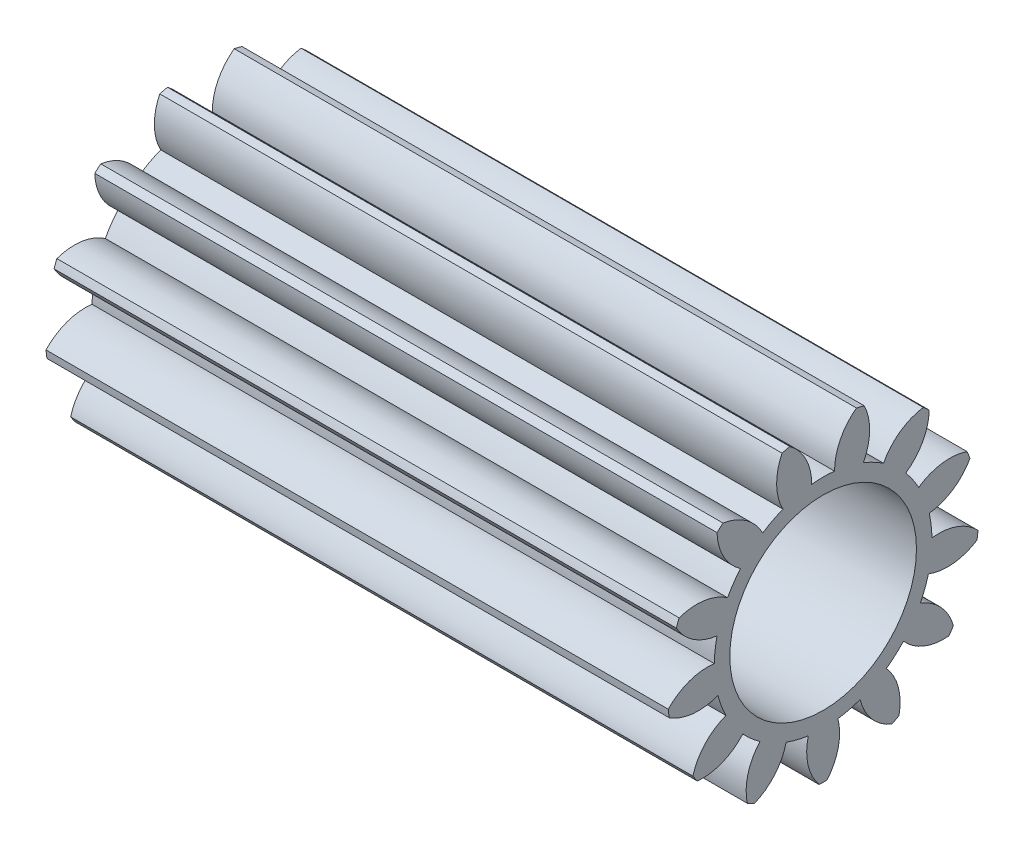
SolidWorks part; units mm, degrees
ref_plane "Plane1" through (0, 0, 0) normal (0, 0, 1) x (1, 0, 0)
ref_plane "Plane2" through (0, 0, 0) normal (0, 1, 0) x (1, 0, 0)
ref_plane "Plane3" through (0, 0, 0) normal (1, 0, 0) x (0, 0, -1)
sketch "HoldingSke" plane through (0, 0, 0) normal (0, 1, 0) x (1, 0, 0)
  line L0 (0, 0) -> (1.9487, -0.4499)
  line L1 (-15, 0) -> (100, 0) construction
  line L2 (0, 0) -> (-2.1039, 2.3779)
  line L3 (0, 0) -> (-11.863, 4.5341)
  line L4 (0, 0) -> (8.4147, 1.9427)
  line L5 (0, 0) -> (-46.8476, -17.4728)
  line L6 (0, 0) -> (-12.4344, -8.3896)
  line L7 (-2.1039, 2.3779) -> (8.6586, 51.2059)
  line L8 (-76.2, 54.61) -> (-75.5, 54.61)
  line L9 (-71.009, 38.7566) -> (-53.1078, 45.2721)
  line L10 (-76.2, 71.12) -> (104.1128, 71.12)
  line L11 (0, 0) -> (-15, 0)
  line L12 (-76.2, 101.6) -> (-76.181, 101.6)
  line L13 (24.9733, 27.94) -> (52.9518, 28.4284)
  line L14 (24.9733, 27.94) -> (24.9743, 27.94)
  line L15 (24.9733, 27.94) -> (100.4006, 29.5858)
  line L16 (-63.627, -0.5) -> (-12.827, -0.5)
  circle A0 centre (0, 0) radius 2.25
  circle A1 centre (0, 0) radius 2.624
  circle A2 centre (0, 0) radius 37.5
  circle A3 centre (0, 0) radius 2.25
  dimension "Num_teeth" = 13
  dimension "Pitch_radius" = 180.3128
  dimension "Width" = 15
  dimension "Thickness" = 15
sketch "BasProSke" plane through (0, 0, 0) normal (0, 1, 0) x (1, 0, 0)
  line L0 (-10, 0) -> (60, 0) construction
  line L1 (0, 0) -> (0, 3.75)
  line L2 (0, 0) -> (15, 0)
  line L3 (15, 0) -> (15, 3.75)
  line L4 (15, 3.75) -> (0, 3.75)
  dimension "Thickness" = 15
  dimension "Diameter" = 7.5
revolve "Base-Revolve" add sketch "BasProSke" angle 360 about L0
sketch "TooCutSke" plane through (0, 0, 0) normal (1, 0, 0) x (0, 0, -1)
  line L1 (0, 0) -> (0, 107) construction
  line L2 (0, 0) -> (-0.425, 3.2221) construction
  line L3 (0, 0) -> (-1.5461, 6.2726) construction
  line L4 (-0.425, 3.2221) -> (-0.773, 3.1363) construction
  arc A0 (0.2752, 2.6095) -> (-0.2752, 2.6095) centre (0, 0) ccw
  arc A1 (0.8316, 3.6827) -> (-0.8316, 3.6827) centre (0, 0) ccw
  circle A2 centre (0, 0) radius 3.25 construction
  circle A3 centre (0, 0) radius 3.054 construction
  arc A4 (-0.2752, 2.6095) -> (-0.8316, 3.6827) centre (-1.5752, 2.6164) ccw
  arc A5 (0.8316, 3.6827) -> (0.2752, 2.6095) centre (1.5752, 2.6164) ccw
extrude "ToothCut" cut sketch "TooCutSke" along normal through all
fillet "Breaks" [suppressed] radius 0.01 tangent propagation no
fillet "RootFillets" [suppressed] radius 0.126
pattern_circular "TeethCuts" count 13 every 27.692 about axis through (-10, 0, 0) along (1, 0, 0) of "ToothCut", "RootFillets", "Breaks"
sketch "HubNeaOneSke" plane through (0, 0, 0) normal (-1, 0, 0) x (0, 0, 1)
  circle A0 centre (0, 0) radius 2.624
  dimension "Diameter" = 5.248
extrude "HubNearOne" [suppressed] add sketch "HubNeaOneSke" along normal blind 35.0001
sketch "HubNeaBotSke" plane through (0, 0, 0) normal (-1, 0, 0) x (0, 0, 1)
  circle A0 centre (0, 0) radius 2.624
  dimension "Diameter" = 5.248
extrude "HubNearBoth" [suppressed] add sketch "HubNeaBotSke" along normal blind 17.5
ref_plane "FarPln" through (15, 0, 0) normal (1, 0, 0) x (0, 0, -1)
sketch "HubFarSke" plane through (15, 0, 0) normal (1, 0, 0) x (0, 0, -1)
  circle A0 centre (0, 0) radius 2.624
  dimension "Diameter" = 5.248
extrude "HubFar" [suppressed] add sketch "HubFarSke" along normal blind 17.5
sketch "BorSke" plane through (0, 0, 0) normal (1, 0, 0) x (0, 0, -1)
  circle A0 centre (0, 0) radius 2.25
  dimension "Diameter" = 4.5
extrude "Bore" cut sketch "BorSke" along normal mid plane 100.0001
sketch "KeySke" plane through (0, 0, 0) normal (1, 0, 0) x (0, 0, -1)
  line L0 (-0.8, 0) -> (-0.8, 2.95)
  line L1 (-0.8, 2.95) -> (0.8, 2.95)
  line L2 (0.8, 2.95) -> (0.8, 0)
  line L3 (0, 0) -> (0, 34) construction
  line L4 (-0.8, 0) -> (0.8, 0)
  dimension "Width" = 1.6
extrude "Keyway" [suppressed] cut sketch "KeySke" along normal mid plane 100.0001
pattern_circular "Keyway2" [suppressed] count 2 every 90 about axis through (-10, 0, 0) along (1, 0, 0)
equation "' \"Module@HoldingSke\" = 6.35"
equation "' \"Num_teeth@HoldingSke\" = 12"
equation "' \"Ap@HoldingSke\" =  20"
equation "' \"Ap@HoldingSke\" = 20"
equation "' \"Width@HoldingSke\" = 0.5 * 25.4"
equation "' \"Hub_dia@HoldingSke\"= 1 * 25.4"
equation "' \"Hub_dia@HoldingSke\" = 1 * 25.4"
equation "' \"Overall_len@HoldingSke\" = 1.0 * 25.4"
equation "' \"Bore@HoldingSke\" = 0.75 * 25.4"
equation "' \"T_dim@HoldingSke\" = 0.1 * 25.4"
equation "' \"Width@KeySke\" = 0.25 * 25.4"
equation "' \"Show_teeth@HoldingSke\" = 13"
equation "' \"Backlash@HoldingSke\" = 0.009 * 25.4"
equation "' \"Addendum_fac@HoldingSke\" = 1.0"
equation "' \"Dedendum_fac@HoldingSke\" = 1.25"
equation "' \"Dedendum_add@HoldingSke\" = 0.00005 * 25.4"
equation "' \"Clearance_fac@HoldingSke\" = 0.25"
equation "\"Pitch@HoldingSke\" = 1 / \"Module@HoldingSke\""
equation "\"Overcut_dia@TooCutSke\" = (\"Num_teeth@HoldingSke\" + 2 * \"Addendum_fac@HoldingSke\") / \"Pitch@HoldingSke\" + 0.002 * 25.4"
equation "\"Pitch_dia@TooCutSke\" = \"Num_teeth@HoldingSke\" / \"Pitch@HoldingSke\""
equation "\"Base_dia@TooCutSke\" = \"Num_teeth@HoldingSke\" / \"Pitch@HoldingSke\" * cos((\"Ap@HoldingSke\"  * 3.14159265 / 180))"
equation "\"Root_dia@TooCutSke\" = (\"Num_teeth@HoldingSke\" + 2) / \"Pitch@HoldingSke\" - 2 * (\"Addendum_fac@HoldingSke\" + \"Dedendum_fac@HoldingSke\") / \"Pitch@HoldingSke\" - \"Dedendum_add@HoldingSke\" * 2"
equation "\"Half_ang@TooCutSke\" = 180 / \"Num_teeth@HoldingSke\""
equation "\"Half_CT@TooCutSke\" = \"Num_teeth@HoldingSke\" / \"Pitch@HoldingSke\" * sin((3.14159265 / 2 / \"Num_teeth@HoldingSke\")) / 2 - 7 * \"Backlash@HoldingSke\" / 4"
equation "\"Flank_rad@TooCutSke\" = \"Num_teeth@HoldingSke\" / \"Pitch@HoldingSke\" / 5"
equation "\"Radius@RootFillets\" = \"Clearance_fac@HoldingSke\" / \"Pitch@HoldingSke\" + \"Dedendum_add@HoldingSke\""
equation "\"Break_rad@Breaks\" = 0.02 / \"Pitch@HoldingSke\""
equation "\"Thickness@HoldingSke\" = \"Width@HoldingSke\""
equation "\"OAL@HoldingSke\" = \"Thickness@HoldingSke\""
equation "\"MHD@HoldingSke\" = (\"Num_teeth@HoldingSke\" + 2) / \"Pitch@HoldingSke\" - 2 * (\"Addendum_fac@HoldingSke\" + \"Dedendum_fac@HoldingSke\")  / \"Pitch@HoldingSke\" - \"Dedendum_add@HoldingSke\" * 2"
equation "\"MBD@HoldingSke\" = (\"Num_teeth@HoldingSke\" + 2) / \"Pitch@HoldingSke\" - 2 * (\"Addendum_fac@HoldingSke\" + \"Dedendum_fac@HoldingSke\")  / \"Pitch@HoldingSke\" - \"Dedendum_add@HoldingSke\" * 2 - 0.002 * 25.4"
equation "\"MHD@HoldingSke\" = ((sgn( \"MHD@HoldingSke\" - \"Hub_dia@HoldingSke\" )-1)*( \"MHD@HoldingSke\" - \"Hub_dia@HoldingSke\" ))/-2+ \"Hub_dia@HoldingSke\""
equation "\"MBD@HoldingSke\" = ((sgn( \"MBD@HoldingSke\" - \"Bore@HoldingSke\" )-1)*( \"MBD@HoldingSke\" - \"Bore@HoldingSke\" ))/-2+ \"Bore@HoldingSke\""
equation "\"OAL@HoldingSke\" = ((sgn( \"OAL@HoldingSke\" - \"Overall_len@HoldingSke\" )+1)*( \"OAL@HoldingSke\" - \"Overall_len@HoldingSke\" ))/2 + \"Overall_len@HoldingSke\" + 0.000002 * 25.4"
equation "\"Num_teeth@TeethCuts\" = int( \"Show_teeth@HoldingSke\" ) + 1"
equation "\"Num_teeth@TeethCuts\" = ((sgn( \"Num_teeth@TeethCuts\" - \"Num_teeth@HoldingSke\" )-1)*( \"Num_teeth@TeethCuts\" - \"Num_teeth@HoldingSke\" ))/-2+ \"Num_teeth@HoldingSke\""
equation "\"Num_teeth@TeethCuts\" = ((sgn( \"Num_teeth@TeethCuts\" - 2.0)+1)*( \"Num_teeth@TeethCuts\" - 2.0))/2 +2.0"
equation "\"Angle@TeethCuts\" = 360.0 / \"Num_teeth@HoldingSke\""
equation "\"Diameter@BasProSke\" = (\"Num_teeth@HoldingSke\" + 2 * \"Addendum_fac@HoldingSke\") / \"Pitch@HoldingSke\""
equation "\"Thickness@BasProSke\"  = \"Thickness@HoldingSke\""
equation "' \"Fillet_rad@BasProSke\" =  \"Thickness@HoldingSke\" * 0.05"
equation "' \"Fillet_rad@BasProSke\" = \"Thickness@HoldingSke\" * 0.05"
equation "\"MHD@HoldingSke\" = ((sgn( \"MHD@HoldingSke\" - \"Root_dia@TooCutSke\" )-1)*( \"MHD@HoldingSke\" - \"Root_dia@TooCutSke\" ))/-2+ \"Root_dia@TooCutSke\""
equation "\"Diameter@HubNeaOneSke\" = \"MHD@HoldingSke\""
equation "\"Length@HubNearOne\" = \"OAL@HoldingSke\" - \"Thickness@BasProSke\""
equation "\"Diameter@HubNeaBotSke\" = \"MHD@HoldingSke\""
equation "\"Length@HubNearBoth\" = ( \"OAL@HoldingSke\" - \"Thickness@BasProSke\" ) / 2.0"
equation "\"Thickness@FarPln\" = \"Thickness@BasProSke\""
equation "\"Diameter@HubFarSke\" = \"MHD@HoldingSke\""
equation "\"Length@HubFar\" = ( \"OAL@HoldingSke\" - \"Thickness@BasProSke\" ) / 2.0"
equation "\"Diameter@BorSke\" = \"MBD@HoldingSke\""
equation "\"D1@Bore\" = \"OAL@HoldingSke\" * 2.0"
equation "\"D1@Keyway\" = \"OAL@HoldingSke\" * 2.0"
equation "\"Offset@KeySke\" = \"T_dim@HoldingSke\" + \"MBD@HoldingSke\" / 2.0"
equation "\"Show_teeth@HoldingSke\"=\"Num_teeth@HoldingSke\""
